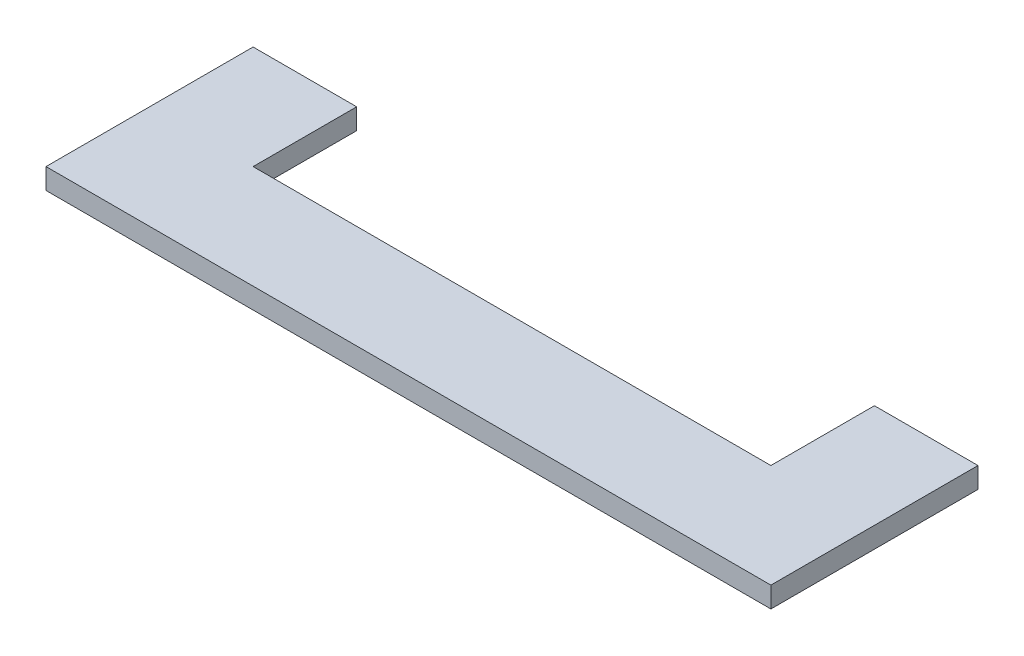
SolidWorks part; units mm, degrees
ref_plane "Front Plane" through (0, 0, 0) normal (0, 0, 1) x (1, 0, 0)
ref_plane "Top Plane" through (0, 0, 0) normal (0, 1, 0) x (1, 0, 0)
ref_plane "Right Plane" through (0, 0, 0) normal (1, 0, 0) x (0, 0, -1)
ref_axis "Axis1" through (0, 0, -39.8625) along (0, 0, 1)
ref_axis "Axis2" through (0, -40.0743, 0) along (0, 1, 0)
ref_axis "Axis3" through (48.4474, 0, 0) along (-1, 0, 0)
sketch "Sketch1" plane through (0, 0, 0) normal (0, 1, 0) x (1, 0, 0)
  line L0 (-90, 0) -> (90, 0) construction
  line L1 (-90, 0) -> (-90, -109) construction
  line L2 (90, 0) -> (90, -109) construction
  line L3 (-105, -49) -> (-75, -49)
  line L4 (-105, -49) -> (-105, -109)
  line L5 (-105, -109) -> (105, -109)
  line L6 (-75, -49) -> (-75, -79)
  line L8 (-105, -109) -> (-105, -49)
  line L10 (105, -109) -> (105, -49)
  line L11 (-75, -79) -> (75, -79)
  line L13 (105, -109) -> (105, -49)
  line L14 (105, -49) -> (75, -49)
  line L15 (75, -79) -> (75, -49)
  point P2 (0, 0)
  point P6 (90, -49)
  point P9 (-75, -110)
  point P11 (-105, -50)
  point P12 (-75, -109)
  point P17 (0, 0)
  point P19 (0, 0)
  point P20 (90, -50)
  point P21 (0, 0)
  point P22 (0, 0)
  point P23 (0, 0)
  point P24 (0, 0)
  point P25 (90, -111)
  point P26 (-90, -49)
  point P27 (0, 0)
  dimension "D1" = 180
  dimension "D2" = 109
  dimension "D6" = 60
extrude "Boss-Extrude1" add sketch "Sketch1" along normal blind 6 contours L15 L11 L6 L3 L4 L5 L10 L14 region at (0, 0, 87.3333)
